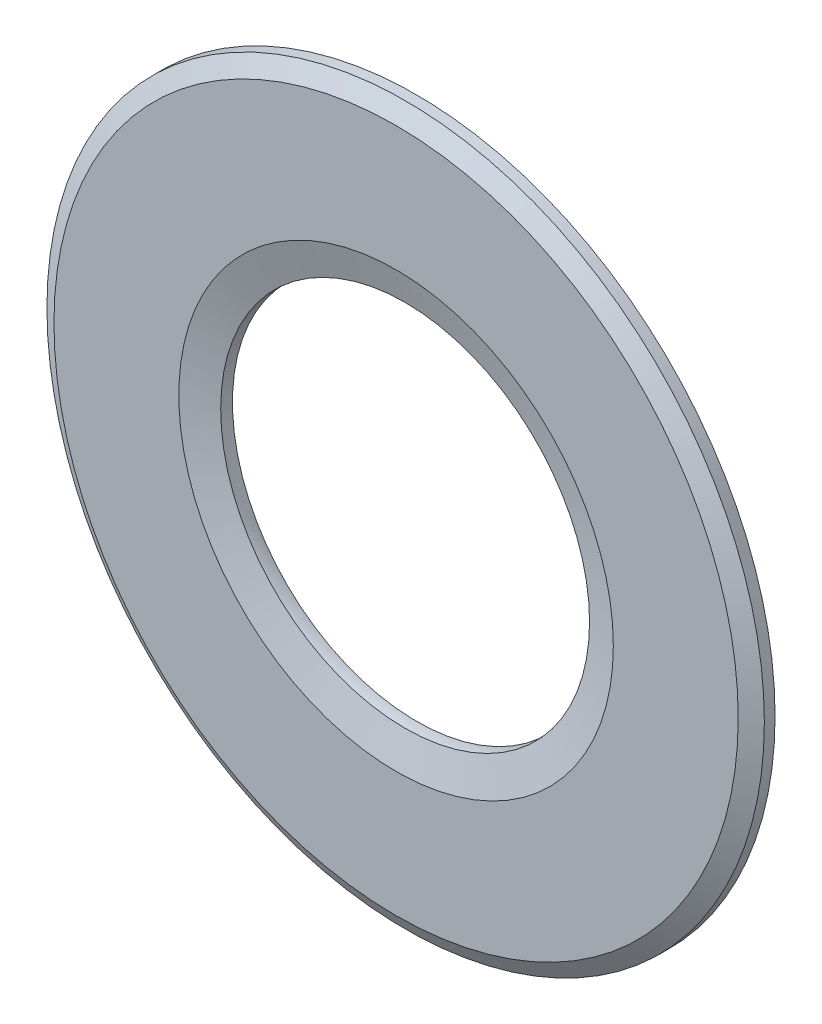
SolidWorks part; units mm, degrees
other "Imported1" parameters "D1"=0.254
ref_plane "Front Plane" through (0, 0, 0) normal (0, 0, 1) x (1, 0, 0)
ref_plane "Top Plane" through (0, 0, 0) normal (0, 1, 0) x (1, 0, 0)
ref_plane "Right Plane" through (0, 0, 0) normal (1, 0, 0) x (0, 0, -1)
sketch "Sketch1" plane through (0, 0, 0) normal (0, 0, 1) x (1, 0, 0)
  line L0 (-9.525, 0) -> (9.525, 0) construction
  line L1 (-4.8895, 0) -> (4.8895, 0) construction
  circle A0 centre (0, 0) radius 4.8895 construction
  circle A1 centre (0, 0) radius 9.525 construction
  point P8 (0, 0)
  point P9 (0, 9.525)
  point P11 (4.8895, 0)
  dimension "ID" = 9.779
  dimension "OD" = 19.05
sketch "Sketch2" plane through (0, 0, 0) normal (1, 0, 0) x (0, 0, -1)
  line L0 (-0.3962, 9.525) -> (0.3962, 9.525) construction
  point P2 (0, 9.525)
  dimension "Thickness" = 0.7925
sketch "Sketch3" plane through (0, 0, 0) normal (0, 0, 1) x (1, 0, 0)
  circle A0 centre (0, 0) radius 4.8895
  circle A1 centre (0, 0) radius 9.525
extrude "Boss-Extrude1" add sketch "Sketch3" along normal up to vertex (0.3962 mm away) and the other way up to vertex (0.3962 mm away) up to point (0, 9.525, 0.3962) other way up to point (0, 9.525, -0.3962)
chamfer "Chamfer1" distance 0.254 angle 60 2 edges at (9.525, 0, -0.3962) (9.525, 0, 0.3962)
sketch "Sketch4" plane through (0, 0, 0) normal (1, 0, 0) x (0, 0, -1)
  line L3 (-0.3962, 4.8387) -> (-0.3962, 4.9403)
  line L4 (-0.3962, 4.8387) -> (0.3962, 4.8387)
  line L5 (0.3962, 4.8387) -> (0.3962, 4.9403)
  line L6 (-0.3962, 0) -> (0.3962, 0) construction
  arc A0 (-0.3962, 4.9403) -> (0.3962, 4.9403) centre (0, 6.4602) ccw
  point P0 (0, 4.8895)
  point P9 (-0.3962, 4.8895)
  point P13 (0, 0)
  dimension "D1" = 0.0508
revolve "Cut-Revolve1" cut sketch "Sketch4" angle 360 about L6
chamfer "Chamfer2" distance 0.254 angle 60 2 edges at (0, -4.9403, -0.3962) (0, -4.9403, 0.3962)
equation "\"D1@Chamfer2\"=\"D1@Chamfer1\""
